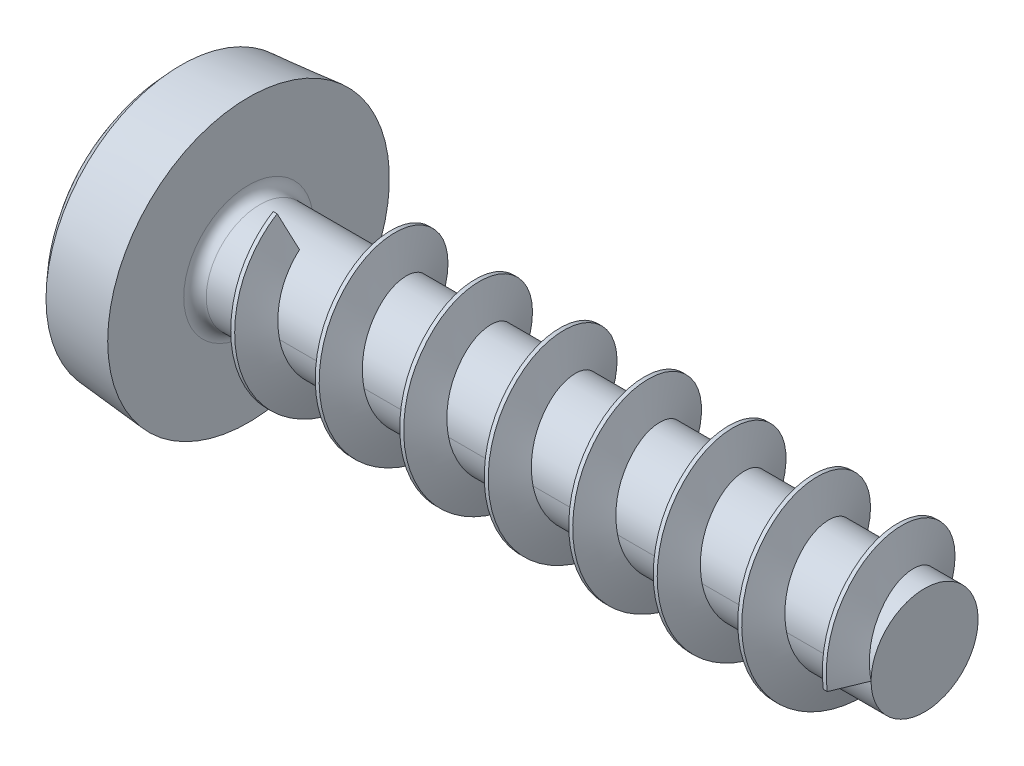
SolidWorks part; units mm, degrees
ref_plane "Front Plane" through (0, 0, 0) normal (0, 0, 1) x (1, 0, 0)
ref_plane "Top Plane" through (0, 0, 0) normal (0, 1, 0) x (1, 0, 0)
ref_plane "Right Plane" through (0, 0, 0) normal (1, 0, 0) x (0, 0, -1)
sketch "Sketch1" plane through (0, 0, 0) normal (0, 0, 1) x (1, 0, 0)
  line L0 (0, 0) -> (6.2042, 0) construction
  line L1 (0.75, 2.395) -> (1.95, 2.5)
  line L2 (1.95, 2.5) -> (1.95, 1.15)
  line L3 (2.15, 0.95) -> (13.95, 0.95)
  line L4 (13.95, 0.95) -> (13.95, 0)
  line L5 (13.95, 0) -> (0, 0)
  arc A0 (0, 0) -> (0.75, 2.395) centre (2.6564, 0.4831) cw
  arc A1 (2.15, 0.95) -> (1.95, 1.15) centre (2.15, 1.15) cw
  point P11 (1.95, 0.95)
  dimension "D6" = 2.7
  dimension "D8" = 0.2
  dimension "D1" = 5
  dimension "D2" = 5
  dimension "D3" = 1.9
  dimension "D4" = 1.95
  dimension "D5" = 1.2
  dimension "D7" = 12
revolve "Revolve1" add sketch "Sketch1" angle 360 about L0
sketch "Sketch2" plane through (13.95, 0, 0) normal (1, 0, 0) x (0, 0, -1)
  circle A0 centre (0, 0) radius 0.95
  dimension "D1" = 1.9
curve "Helix/Spiral1" pitch 1.5 height 10.8 radius 0.95 centre (13.95, 0, 0) axis (-1, 0, 0) start towards (0, 0, 1)
sketch "Sketch3" plane through (0, 0, 0) normal (0, 1, 0) x (1, 0, 0)
  line L0 (-0.1237, 0) -> (5.8686, 0) construction
  line L1 (13.95, -0.95) -> (13.7222, -1.5)
  line L2 (13.7222, -1.5) -> (13.6522, -1.5)
  line L3 (13.6522, -1.5) -> (13.4244, -0.95)
  line L4 (2.15, -0.95) -> (13.95, -0.95) construction
  line L5 (13.4244, -0.95) -> (13.95, -0.95)
  dimension "D1" = 45
  dimension "D2" = 0.07
  dimension "D3" = 3
sweep "Sweep1" add profiles "Sketch3" path "Helix/Spiral1"
ref_plane "Plane1" through (1.1, 0, 0) normal (1, 0, 0) x (0, 0, -1)
sketch "Sketch4" plane through (1.1, 0, 0) normal (1, 0, 0) x (0, 0, -1)
  line L0 (0, 0) -> (0, 1.0777) construction
  line L1 (0, 0) -> (-0.5044, 0.8737) construction
  line L2 (0, 0) -> (-0.9621, 0.5555) construction
  line L3 (0, 0) -> (-0.8717, -0.5033) construction
  line L5 (-1.366, -0.0181) -> (-1.3635, 0.0331) construction
  circle A0 centre (0, 0) radius 1.2 construction
  circle A1 centre (0, 0) radius 0.85 construction
  arc A2 (0, 1.2) -> (-0.1984, 1.0393) centre (0.0058, 0.9901) ccw
  arc A3 (-0.1984, 1.0393) -> (-0.425, 0.7361) centre (-0.665, 1.1518) cw
  arc A4 (-0.8009, 0.6914) -> (-0.425, 0.7361) centre (-0.665, 1.1518) ccw
  arc A5 (-1.0392, 0.6) -> (-0.8009, 0.6914) centre (-0.8603, 0.49) cw
  arc A6 (-1.0392, 0.6) -> (-0.9992, 0.3479) centre (-0.8545, 0.5) ccw
  arc A7 (-0.9992, 0.3479) -> (-0.85, 0) centre (-1.33, 0) cw
  arc A8 (-0.9992, -0.3479) -> (-0.85, 0) centre (-1.33, 0) ccw
  arc A9 (-1.0392, -0.6) -> (-0.9992, -0.3479) centre (-0.8545, -0.5) cw
  arc A10 (-1.0392, -0.6) -> (-0.8009, -0.6914) centre (-0.8603, -0.49) ccw
  arc A11 (-0.8009, -0.6914) -> (-0.425, -0.7361) centre (-0.665, -1.1518) cw
  arc A12 (-0.1984, -1.0393) -> (-0.425, -0.7361) centre (-0.665, -1.1518) ccw
  arc A13 (0, -1.2) -> (-0.1984, -1.0393) centre (0.0058, -0.9901) cw
  arc A14 (0, -1.2) -> (0.1984, -1.0393) centre (-0.0058, -0.9901) ccw
  arc A15 (0.1984, -1.0393) -> (0.425, -0.7361) centre (0.665, -1.1518) cw
  arc A16 (0.8009, -0.6914) -> (0.425, -0.7361) centre (0.665, -1.1518) ccw
  arc A17 (1.0392, -0.6) -> (0.8009, -0.6914) centre (0.8603, -0.49) cw
  arc A18 (1.0392, -0.6) -> (0.9992, -0.3479) centre (0.8545, -0.5) ccw
  arc A19 (0.9992, -0.3479) -> (0.85, 0) centre (1.33, 0) cw
  arc A20 (0.9992, 0.3479) -> (0.85, 0) centre (1.33, 0) ccw
  arc A21 (1.0392, 0.6) -> (0.9992, 0.3479) centre (0.8545, 0.5) cw
  arc A22 (1.0392, 0.6) -> (0.8009, 0.6914) centre (0.8603, 0.49) ccw
  arc A23 (0.8009, 0.6914) -> (0.425, 0.7361) centre (0.665, 1.1518) cw
  arc A24 (0.1984, 1.0393) -> (0.425, 0.7361) centre (0.665, 1.1518) ccw
  arc A25 (0, 1.2) -> (0.1984, 1.0393) centre (-0.0058, 0.9901) cw
  dimension "D1" = 2.4
  dimension "D2" = 1.7
  dimension "D4" = 0.21
  dimension "D5" = 0.48
extrude "Cut-Extrude1" cut sketch "Sketch4" against normal blind 10
sketch "Sketch5" plane through (0, 0, 0) normal (1, 0, 0) x (0, 0, -1)
  circle A0 centre (0, 0) radius 1.2
  dimension "D1" = 2.4
extrude "Cut-Extrude2" cut sketch "Sketch5" along normal mid plane 0.5
